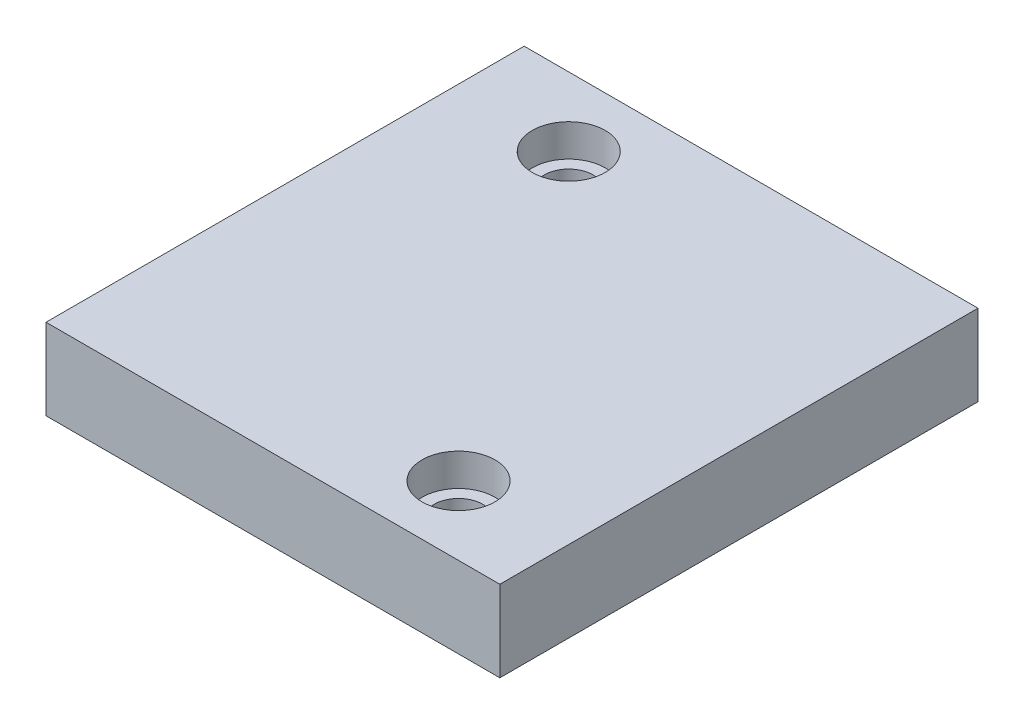
SolidWorks part; units mm, degrees
other "标注1"
sketch "草图3" plane through (0, 5, 29.5) normal (-0.6417, 0.7662, 0.0339) x (0.7661, 0.6384, 0.0747)
ref_plane "前视基准面" through (0, 0, 0) normal (0, 0, 1) x (1, 0, 0)
ref_plane "上视基准面" through (0, 0, 0) normal (0, 1, 0) x (1, 0, 0)
ref_plane "右视基准面" through (0, 0, 0) normal (1, 0, 0) x (0, 0, -1)
other "Configuration Table"
sketch "草图1" plane through (0, 0, 0) normal (0, 1, 0) x (1, 0, 0)
  line L33 (-28, -29.5) -> (0, -29.5)
  line L34 (-28, -29.5) -> (-28, 0)
  line L36 (0, -29.5) -> (0, 0)
  line L37 (-28, 0) -> (0, 0)
  circle A12 centre (-21, -4.25) radius 1.5
  circle A13 centre (-21, -4.25) radius 2.25
  circle A14 centre (-6.8, -25.25) radius 1.5
  circle A15 centre (-6.8, -25.25) radius 2.25
  point P0 (-90.6464, 22.0667)
  point P11 (0, 0)
  point P12 (0, 0)
  dimension "D1" = 28
  dimension "D2" = 29.5
  dimension "D3" = 3
  dimension "D4" = 4.5
extrude "凸台-拉伸1" add sketch "草图1" along normal blind 5 contours L34 | L36 L37 L34 L33
extrude "切除-拉伸1" cut sketch "草图1<20>" along normal through all contours A12 | A14
sketch "草图1<20>" plane through (0, 0, 0) normal (0, 1, 0) x (1, 0, 0) same geometry as "草图1"
extrude "切除-拉伸2" cut sketch "草图1<21>" against normal blind 2 from surface contours A13 | A15 starting at face at (-21, 5, 5.75)
sketch "草图1<21>" plane through (0, 0, 0) normal (0, 1, 0) x (1, 0, 0) same geometry as "草图1"
sketch "草图4" plane through (-28, 0, 0) normal (-1, 0, 0) x (0, 0, 1)
  line L1 (0, 5) -> (0, 0) construction
  line L2 (29.5, 5) -> (29.5, 0) construction
  circle A0 centre (10, 2.5) radius 1
  circle A1 centre (24.5, 2.5) radius 1
  point P4 (0, 0)
  point P9 (0, 2.5)
  dimension "D1" = 2
  dimension "D2" = 10
  dimension "D3" = 5
extrude "切除-拉伸3" cut sketch "草图4" against normal blind 4
